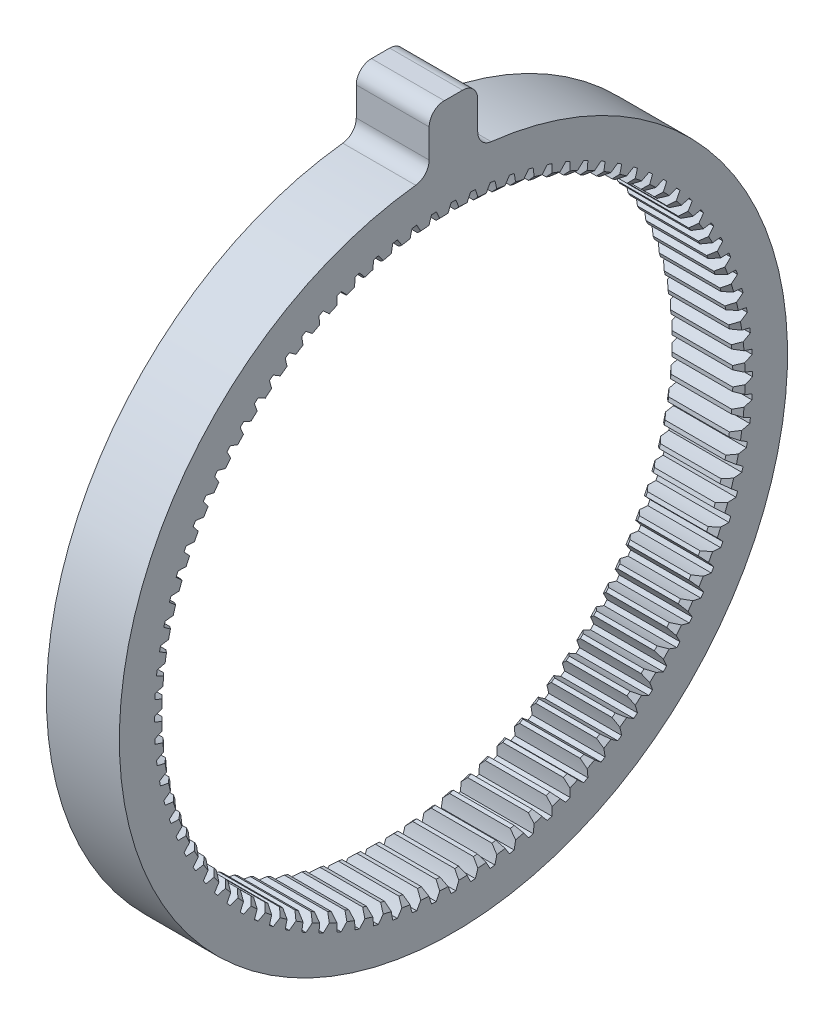
SolidWorks part; units mm, degrees
material "Custom Plastic"
ref_plane "Plane1" through (0, 0, 0) normal (0, 0, 1) x (1, 0, 0)
ref_plane "Plane2" through (0, 0, 0) normal (0, 1, 0) x (1, 0, 0)
ref_plane "Plane3" through (0, 0, 0) normal (1, 0, 0) x (0, 0, -1)
sketch "HoldingSke" plane through (0, 0, 0) normal (0, 1, 0) x (1, 0, 0)
  line L0 (0, 0) -> (-0.1045, -0.9945)
  line L1 (-15, 0) -> (100, 0) construction
  line L2 (0, 0) -> (-2.1039, 2.3779)
  line L3 (0, 0) -> (-11.863, 4.5341)
  line L4 (0, 0) -> (-0.9027, 8.5887)
  line L5 (0, 0) -> (-23.7986, -8.8762)
  line L6 (0, 0) -> (-10.5278, -7.1032)
  line L7 (-2.1039, 2.3779) -> (3.3635, 27.1825)
  line L8 (-76.2, 3.3779) -> (-54.61, 3.3779)
  line L9 (-71.009, 38.7566) -> (-53.1078, 45.2721)
  line L10 (-76.2, 71.12) -> (104.1128, 71.12)
  line L11 (0, 0) -> (-12, 0)
  line L12 (-76.2, 101.6) -> (-76.162, 101.6)
  line L13 (24.9733, 27.94) -> (52.9518, 28.4284)
  line L14 (24.9733, 27.94) -> (24.9743, 27.94)
  line L15 (24.9733, 27.94) -> (100.4006, 29.5858)
  circle A0 centre (0, 0) radius 55
  circle A1 centre (0, 0) radius 12.7
  circle A2 centre (0, 0) radius 12.7
  dimension "MHD" = 25.4
  dimension "Hub_dia" = 25.4
  dimension "Diameter" = 110
  dimension "Num_teeth" = 96
  dimension "Pitch" = 1
  dimension "Overall_len" = 25.4
  dimension "Show_teeth" = 96
  dimension "Thickness" = 12.7
  dimension "OAL" = 25.4001
  dimension "T_dim" = 21.59
  dimension "Ap" = 20
  dimension "H" = 19.05
  dimension "Pitch_radius" = 180.3128
  dimension "Width" = 12
  dimension "Backlash" = 0.038
  dimension "Addendum_fac" = 1
  dimension "Dedendum_fac" = 1.25
  dimension "Clearance_fac" = 0.25
  dimension "Dedendum_add" = 0.001
  dimension "Module" = 1
sketch "BasProSke" plane through (0, 0, 0) normal (0, 1, 0) x (1, 0, 0)
  line L0 (-10, 0) -> (60, 0) construction
  line L1 (0, 47) -> (0, 55)
  line L2 (0, 47) -> (12, 47)
  line L3 (12, 47) -> (12, 55)
  line L4 (12, 55) -> (0, 55)
  dimension "Diameter" = 110
  dimension "Thickness" = 12
  dimension "Inside_diameter" = 94
revolve "Base-Revolve" add sketch "BasProSke" angle 360 about L0
chamfer "Chamfer1" distance 1 angle 45 2 edges at (0, 0, 47) (12, 0, 47)
sketch "TooCutSke" plane through (0, 0, 0) normal (1, 0, 0) x (0, 0, -1)
  line L3 (0.8804, 47.9919) -> (0.8804, 53.6633) construction
  line L4 (0, 0) -> (0, 59.563) construction
  line L5 (0, 0) -> (-2.2356, 68.2909) construction
  line L6 (-21.7163, 39.9055) -> (36.4943, 41.8112) construction
  circle A0 centre (0, 0) radius 48 construction
  circle A1 centre (0, 0) radius 49.251 construction
  circle A2 centre (0, 0) radius 40.5947 construction
  circle A3 centre (0, 0) radius 46.9746 construction
  arc A4 (1.2239, 46.9587) -> (0.39, 49.2495) centre (-21.7163, 39.9055) ccw
  arc A5 (1.2239, 46.9587) -> (-1.2239, 46.9587) centre (0, 0) ccw
  arc A6 (0.39, 49.2495) -> (-0.39, 49.2495) centre (0, 0) ccw
  arc A7 (-0.39, 49.2495) -> (-1.2239, 46.9587) centre (21.7163, 39.9055) ccw
  dimension "Pitch_dia" = 96
  dimension "Base_dia" = 81.1894
  dimension "Root_dia" = 98.502
  dimension "Overcut_dia" = 93.9492
  dimension "Flank_rad" = 24
  dimension "Half_ang" = 1.875
  dimension "Half_CT" = 0.8804
extrude "ToothCut" cut sketch "TooCutSke" along normal through all
pattern_circular "TeethCuts" count 96 every 3.75 about axis through (-10, 0, 0) along (1, 0, 0) of "ToothCut"
sketch "Sketch1" plane through (12, 0, 0) normal (1, 0, 0) x (0, 0, -1)
  line L1 (-4, 52.3474) -> (4, 52.3474)
  line L2 (-4, 52.3474) -> (-4, 64.3474)
  line L3 (-4, 64.3474) -> (4, 64.3474)
  line L4 (4, 52.3474) -> (4, 64.3474)
  circle A3 centre (0, 0) radius 52.5
  circle A4 centre (0, 0) radius 52.5 construction
  point P4 (0, 52.3474)
  point P5 (0, 0)
  point P7 (4, 53.1235)
  point P8 (4, 52.3474)
  point P9 (0, 0)
  dimension "D1" = 12
  dimension "D2" = 8
  dimension "D3" = 2.5
extrude "Boss-Extrude1" add sketch "Sketch1" against normal up to surface (12 mm away) up to face at (0, 0, 55)
fillet "Fillet1" radius 2.5 4 edges at (6, 64.3474, 4) (6, 64.3474, -4) (6, 54.8544, -4) (6, 54.8544, 4)
equation "' \"Module@HoldingSke\" = 6.35"
equation "' \"Num_teeth@HoldingSke\" = 24"
equation "' \"Ap@HoldingSke\" =  14.5"
equation "' \"Ap@HoldingSke\" = 14.5"
equation "' \"Width@HoldingSke\" = 12"
equation "' \"Diameter@HoldingSke\" = 8 * 25.4"
equation "' \"Show_teeth@HoldingSke\" = 100"
equation "' \"Backlash@HoldingSke\" = 0.009 * 25.4"
equation "' \"Addendum_fac@HoldingSke\" = 1.0"
equation "' \"Dedendum_fac@HoldingSke\" = 1.25"
equation "' \"Dedendum_add@HoldingSke\" = 0.00005 * 25.4"
equation "' \"Clearance_fac@HoldingSke\" = 0.25"
equation "\"Pitch@HoldingSke\" = 1 / \"Module@HoldingSke\" "
equation "\"Overcut_dia@TooCutSke\" = (\"Num_teeth@HoldingSke\" - 2 * \"Addendum_fac@HoldingSke\") / \"Pitch@HoldingSke\" - 0.002 * 25.4"
equation "\"Pitch_dia@TooCutSke\" = \"Num_teeth@HoldingSke\" / \"Pitch@HoldingSke\""
equation "\"Base_dia@TooCutSke\" = \"Num_teeth@HoldingSke\" / \"Pitch@HoldingSke\" * cos((\"Ap@HoldingSke\"  * 3.14159265 / 180)) * 0.90"
equation "\"Root_dia@TooCutSke\" = \"Num_teeth@HoldingSke\"  / \"Pitch@HoldingSke\" + 2 *  \"Dedendum_fac@HoldingSke\"/ \"Pitch@HoldingSke\" + \"Dedendum_add@HoldingSke\" * 2"
equation "\"Half_ang@TooCutSke\" = 180 / \"Num_teeth@HoldingSke\""
equation "\"Half_CT@TooCutSke\" = \"Num_teeth@HoldingSke\" / \"Pitch@HoldingSke\" * sin((3.14159265 / 2 / \"Num_teeth@HoldingSke\")) / 2 + 10 * \"Backlash@HoldingSke\" / 4"
equation "\"Flank_rad@TooCutSke\" = \"Num_teeth@HoldingSke\" / \"Pitch@HoldingSke\" / 4"
equation "\"Num_teeth@TeethCuts\" = int( \"Show_teeth@HoldingSke\" ) + 1"
equation "\"Num_teeth@TeethCuts\" = ((sgn( \"Num_teeth@TeethCuts\" - \"Num_teeth@HoldingSke\" )-1)*( \"Num_teeth@TeethCuts\" - \"Num_teeth@HoldingSke\" ))/-2+ \"Num_teeth@HoldingSke\""
equation "\"Num_teeth@TeethCuts\" = ((sgn( \"Num_teeth@TeethCuts\" - 2.0)+1)*( \"Num_teeth@TeethCuts\" - 2.0))/2 +2.0"
equation "\"Angle@TeethCuts\" = 360.0 / \"Num_teeth@HoldingSke\""
equation "\"Diameter@BasProSke\" = \"Num_teeth@HoldingSke\"  / \"Pitch@HoldingSke\" + 2 *  \"Dedendum_fac@HoldingSke\"/ \"Pitch@HoldingSke\" + \"Dedendum_add@HoldingSke\" * 2 + 0.002 * 25.4"
equation "\"Diameter@BasProSke\" = ((sgn( \"Diameter@BasProSke\"  - \"Diameter@HoldingSke\" )+1)*( \"Diameter@BasProSke\"  - \"Diameter@HoldingSke\" ))/2 + \"Diameter@HoldingSke\""
equation "\"Inside_diameter@BasProSke\" =  (\"Num_teeth@HoldingSke\" - 2 * \"Addendum_fac@HoldingSke\") / \"Pitch@HoldingSke\" "
equation "\"Thickness@BasProSke\"  = \"Width@HoldingSke\""
